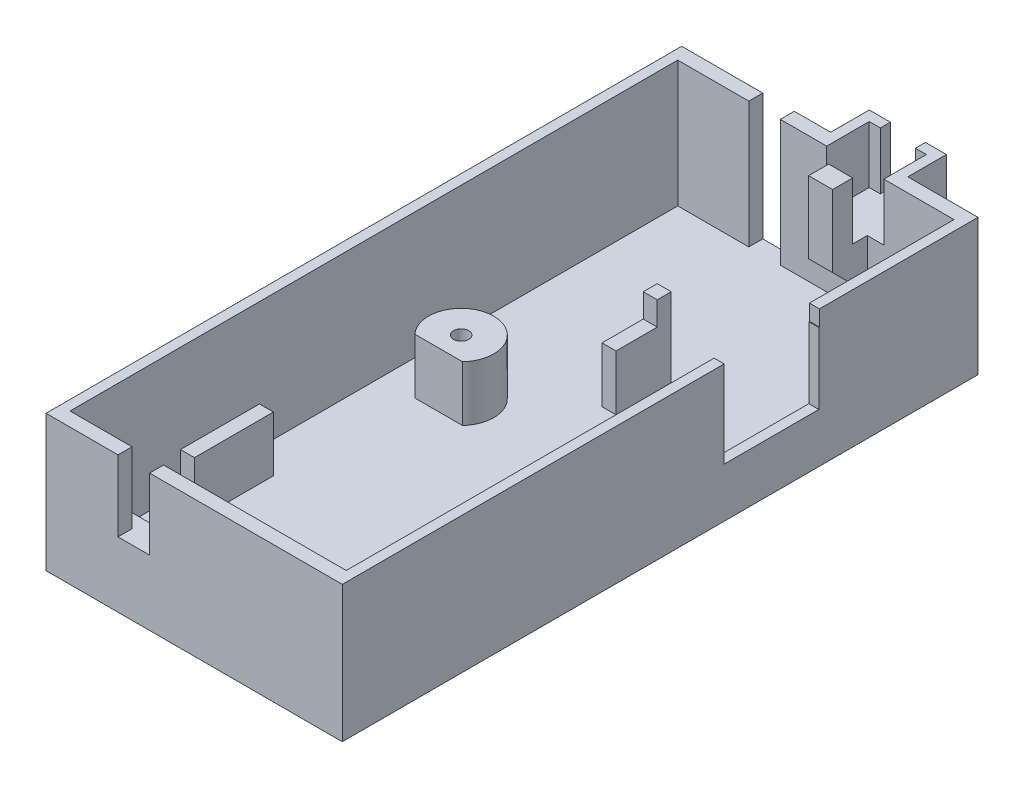
SolidWorks part; units mm, degrees
ref_plane "Front Plane" through (0, 0, 0) normal (0, 0, 1) x (1, 0, 0)
ref_plane "Top Plane" through (0, 0, 0) normal (0, 1, 0) x (1, 0, 0)
ref_plane "Right Plane" through (0, 0, 0) normal (1, 0, 0) x (0, 0, -1)
sketch "Sketch2" plane through (0, 0, 0) normal (0, 0, 1) x (1, 0, 0)
  line L0 (-30.2154, 3.088) -> (-30.2154, -12.912)
  line L1 (-30.2154, -12.912) -> (4.7846, -12.912)
  line L2 (4.7846, -12.912) -> (4.7846, 3.088)
  line L3 (-31.4854, 3.088) -> (-31.4854, -14.182)
  line L4 (-31.4854, -14.182) -> (6.0546, -14.182)
  line L5 (6.0546, -14.182) -> (6.0546, 3.088)
  line L6 (-31.4854, 3.088) -> (-30.2154, 3.088)
  line L7 (4.7846, 3.088) -> (6.0546, 3.088)
  dimension "D1" = 16
  dimension "D2" = 16
  dimension "D3" = 35
  dimension "D4" = 1.27
extrude "Boss-Extrude1" add sketch "Sketch2" along normal blind 77
sketch "Sketch3" plane through (0, 0, 77) normal (0, 0, 1) x (1, 0, 0)
  line L1 (-31.4854, 3.088) -> (6.0546, 3.088)
  line L2 (-31.4854, 3.088) -> (-31.4854, -14.182)
  line L3 (-31.4854, -14.182) -> (6.0546, -14.182)
  line L4 (6.0546, 3.088) -> (6.0546, -14.182)
extrude "Boss-Extrude2" add sketch "Sketch3" along normal blind 1.77
sketch "Sketch4" plane through (0, 0, 0) normal (0, 0, -1) x (-1, 0, 0)
  line L1 (-6.0546, 3.088) -> (31.4854, 3.088)
  line L2 (-6.0546, 3.088) -> (-6.0546, -14.182)
  line L3 (-6.0546, -14.182) -> (31.4854, -14.182)
  line L4 (31.4854, 3.088) -> (31.4854, -14.182)
extrude "Boss-Extrude3" add sketch "Sketch4" along normal blind 1.77
sketch "Sketch5" plane through (0, 0, -1.77) normal (0, 0, -1) x (-1, 0, 0)
  line L0 (31.4854, 3.088) -> (-6.0546, 3.088) construction
  line L1 (17.2154, 3.088) -> (21.2154, 3.088)
  line L2 (17.2154, 3.088) -> (17.2154, -12.912)
  line L3 (17.2154, -12.912) -> (21.2154, -12.912)
  line L4 (21.2154, 3.088) -> (21.2154, -12.912)
  line L5 (-4.7846, -12.912) -> (30.2154, -12.912) construction
  line L6 (30.2154, -12.912) -> (30.2154, 3.088) construction
  dimension "D1" = 4
  dimension "D2" = 9
extrude "Cut-Extrude2" cut sketch "Sketch5" against normal blind 1.77
sketch "Sketch6" plane through (0, 3.088, 0) normal (0, 1, 0) x (1, 0, 0)
  line L0 (4.7846, -77) -> (4.7846, 0) construction
  line L1 (-11.3454, 5.39) -> (-4.1054, 5.39)
  line L2 (-11.3454, 5.39) -> (-11.3454, -1.85)
  line L3 (-11.3454, -1.85) -> (-4.1054, -1.85)
  line L4 (-4.1054, 5.39) -> (-4.1054, -1.85)
  line L5 (-12.6154, 6.66) -> (-2.8354, 6.66)
  line L6 (-12.6154, 6.66) -> (-12.6154, -4.39)
  line L7 (-12.6154, -4.39) -> (-2.8354, -4.39)
  line L8 (-2.8354, 6.66) -> (-2.8354, -4.39)
  line L9 (-17.2154, 1.77) -> (6.0546, 1.77) construction
  dimension "D1" = 1.27
  dimension "D2" = 1.27
  dimension "D3" = 8.89
  dimension "D4" = 7.24
  dimension "D5" = 1.27
  dimension "D6" = 2.54
  dimension "D7" = 7.24
  dimension "D8" = 3.62
extrude "button_walls" add sketch "Sketch6" against normal blind 7.24
sketch "Sketch7" plane through (0, -4.152, 0) normal (0, -1, 0) x (1, 0, 0)
  line L1 (-12.6154, 4.39) -> (-2.8354, 4.39)
  line L2 (-12.6154, 4.39) -> (-12.6154, -6.66)
  line L3 (-12.6154, -6.66) -> (-2.8354, -6.66)
  line L4 (-2.8354, 4.39) -> (-2.8354, -6.66)
extrude "button_bottom" add sketch "Sketch7" along normal blind 1.27
sketch "Sketch8" plane through (0, 3.088, 0) normal (0, 1, 0) x (1, 0, 0)
  line L0 (-11.3454, 0) -> (-4.1054, 0) construction
  line L1 (-11.3454, 1.77) -> (-4.1054, 1.77)
  line L2 (-11.3454, 1.77) -> (-11.3454, 0)
  line L3 (-11.3454, 0) -> (-4.1054, 0)
  line L4 (-4.1054, 1.77) -> (-4.1054, 0)
extrude "button_cutout_middle" cut sketch "Sketch8" against normal blind 7.24
sketch "Sketch9" plane through (0, 3.088, 0) normal (0, 1, 0) x (1, 0, 0)
  line L0 (-7.7254, 9.378) -> (-7.7254, -7.9569) construction
  line L1 (-2.8354, 6.66) -> (-12.6154, 6.66) construction
  line L2 (-9.9454, 6.66) -> (-5.4954, 6.66)
  line L3 (-9.9454, 6.66) -> (-9.9454, 5.39)
  line L4 (-9.9454, 5.39) -> (-5.4954, 5.39)
  line L5 (-5.4954, 6.66) -> (-5.4954, 5.39)
  line L6 (-4.1054, 5.39) -> (-11.3454, 5.39) construction
  line L13 (-12.6154, -4.39) -> (-2.8354, -4.39) construction
  line L14 (-12.6154, 0) -> (-9.2454, 0)
  line L15 (-12.6154, 0) -> (-12.6154, -4.39)
  line L16 (-12.6154, -4.39) -> (-9.2454, -4.39)
  line L17 (-9.2454, 0) -> (-9.2454, -4.39)
  line L19 (-2.8354, 0) -> (-6.2054, 0)
  line L20 (-2.8354, 0) -> (-2.8354, -4.39)
  line L21 (-2.8354, -4.39) -> (-6.2054, -4.39)
  line L22 (-6.2054, 0) -> (-6.2054, -4.39)
  dimension "D1" = 4.45
  dimension "D2" = 2.22
  dimension "D3" = 1.52
  dimension "D4" = 1.52
extrude "button_cutout_front_back" cut sketch "Sketch9" against normal blind 7.24
sketch "Sketch10" plane through (0, -4.152, 0) normal (0, 1, 0) x (1, 0, 0)
  line L1 (-12.6154, 0) -> (-9.2454, 0)
  line L2 (-12.6154, 0) -> (-12.6154, -4.39)
  line L3 (-12.6154, -4.39) -> (-9.2454, -4.39)
  line L4 (-9.2454, 0) -> (-9.2454, -4.39)
  line L5 (-2.8354, 0) -> (-6.2054, 0)
  line L6 (-2.8354, 0) -> (-2.8354, -4.39)
  line L7 (-2.8354, -4.39) -> (-6.2054, -4.39)
  line L8 (-6.2054, 0) -> (-6.2054, -4.39)
extrude "button_cutout_bottom" cut sketch "Sketch10" against normal blind 1.27
chamfer "button_Chamfer1" distance 5 angle 45 1 edges at (-7.7254, -5.422, 0)
sketch "Sketch12" plane through (0, -12.912, 0) normal (0, 1, 0) x (1, 0, 0)
  line L0 (4.7846, -77) -> (-30.2154, -77) construction
  line L1 (-30.2154, -77) -> (4.7846, -77)
  line L2 (-30.2154, -77) -> (-30.2154, -75.23)
  line L3 (-30.2154, -75.23) -> (4.7846, -75.23)
  line L4 (4.7846, -77) -> (4.7846, -75.23)
  line L5 (4.7846, -77) -> (4.7846, 0) construction
  line L11 (4.7846, -77) -> (4.7846, 0) construction
  line L12 (-27.9854, -55.23) -> (-26.2154, -55.23)
  line L13 (-27.9854, -55.23) -> (-27.9854, -65.23)
  line L14 (-27.9854, -65.23) -> (-26.2154, -65.23)
  line L15 (-26.2154, -55.23) -> (-26.2154, -65.23)
  line L16 (4.7846, -37.73) -> (-60.4587, -37.73) construction
  line L17 (-2.7154, -35.96) -> (4.7846, -35.96)
  line L18 (-2.7154, -35.96) -> (-2.7154, -37.73)
  line L19 (-2.7154, -37.73) -> (4.7846, -37.73)
  line L20 (4.7846, -35.96) -> (4.7846, -37.73)
  line L21 (-25.7839, -37.73) -> (-19.7648, -37.73)
  line L22 (-54.4351, -21.6) -> (25.4799, -21.6) construction
  line L24 (-12.9854, -19.83) -> (-11.2154, -19.83)
  line L25 (-12.9854, -19.83) -> (-12.9854, -26.83)
  line L26 (-12.9854, -26.83) -> (-11.2154, -26.83)
  line L27 (-11.2154, -19.83) -> (-11.2154, -26.83)
  arc A0 (-19.7648, -37.73) -> (-25.7839, -37.73) centre (-22.7744, -34.8868) ccw
  circle A1 centre (-22.7744, -34.8868) radius 0.9652
  point P29 (-12.1004, -19.83)
  dimension "D11" = 8.2804
  dimension "D12" = 1.9304
  dimension "D1" = 1.77
  dimension "D2" = 31
  dimension "D3" = 1.77
  dimension "D4" = 10
  dimension "D5" = 10
  dimension "D6" = 1.77
  dimension "D7" = 7.5
  dimension "D8" = 37.5
  dimension "D9" = 42.1132
  dimension "D10" = 27.559
  dimension "D13" = 55.4
  dimension "D14" = 1.77
  dimension "D15" = 7
  dimension "D16" = 1.77
  dimension "D17" = 16
extrude "support_pcb_battery" add sketch "Sketch12" along normal blind 7
sketch "Sketch13" plane through (6.0546, 0, 0) normal (1, 0, 0) x (0, 0, -1)
  line L0 (-77, 3.088) -> (-77, -22.3902) construction
  line L1 (-81.5091, -5.912) -> (21.2567, -5.912) construction
  line L3 (-30.3952, 1.088) -> (-18.3952, 1.088)
  line L4 (-30.3952, 1.088) -> (-30.3952, -7.912)
  line L5 (-30.3952, -7.912) -> (-18.3952, -7.912)
  line L6 (-18.3952, 1.088) -> (-18.3952, -7.912)
  point P10 (-18.3952, -3.412)
  dimension "D1" = 12
  dimension "D2" = 2.5
  dimension "D3" = 9
extrude "cutout_usb" cut sketch "Sketch13" against normal blind 5
sketch "Sketch14" plane through (6.0546, 0, 0) normal (1, 0, 0) x (0, 0, -1)
  line L1 (-30.3952, 1.088) -> (-18.3185, 1.088)
  line L2 (-30.3952, 1.088) -> (-30.3952, 4.9259)
  line L3 (-30.3952, 4.9259) -> (-18.3185, 4.9259)
  line L4 (-18.3185, 1.088) -> (-18.3185, 4.9259)
extrude "cutout_temporary" cut sketch "Sketch14" against normal blind 5
sketch "Sketch16" plane through (0, -5.912, 0) normal (0, 1, 0) x (1, 0, 0)
  line L0 (-11.2154, -26.83) -> (-11.2154, -19.83) construction
  line L1 (-12.9854, -19.83) -> (-11.2154, -19.83)
  line L2 (-12.9854, -19.83) -> (-12.9854, -21.6)
  line L3 (-12.9854, -21.6) -> (-11.2154, -21.6)
  line L4 (-11.2154, -19.83) -> (-11.2154, -21.6)
  dimension "D1" = 1.77
extrude "tab_pcb_retainer" add sketch "Sketch16" along normal blind 3
sketch "Sketch17" plane through (0, 3.088, 0) normal (0, 1, 0) x (1, 0, 0)
  line L0 (4.7846, -77) -> (-30.2154, -77) construction
  line L1 (-22.3614, -77) -> (-18.3614, -77)
  line L2 (-22.3614, -77) -> (-22.3614, -78.77)
  line L3 (-22.3614, -78.77) -> (-18.3614, -78.77)
  line L4 (-18.3614, -77) -> (-18.3614, -78.77)
  line L5 (6.0546, -78.77) -> (-31.4854, -78.77) construction
  line L7 (4.7846, -77) -> (4.7846, -30.3952) construction
  point P8 (-20.3614, -77)
  dimension "D1" = 25.146
  dimension "D2" = 4
extrude "cutout_back_mot_wires" cut sketch "Sketch17" against normal up to surface (9 mm away) up to face at (-12.7154, -5.912, 76.115)
